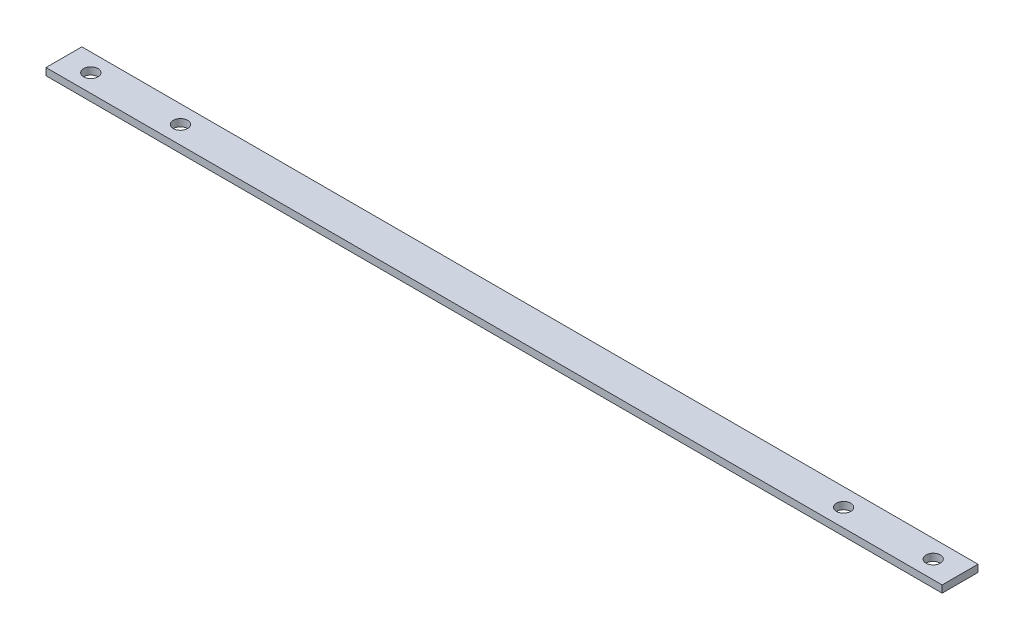
SolidWorks part; units mm, degrees
ref_plane "Спереди" through (0, 0, 0) normal (0, 0, 1) x (1, 0, 0)
ref_plane "Сверху" through (0, 0, 0) normal (0, 1, 0) x (1, 0, 0)
ref_plane "Справа" through (0, 0, 0) normal (1, 0, 0) x (0, 0, -1)
sketch "Эскиз1" plane through (0, 0, 0) normal (1, 0, 0) x (0, 0, -1)
  line L0 (0, 0) -> (20, 0)
extrude "Вытянуть-Тонкостенный1" add sketch "Эскиз1" along normal blind 500 thin thin type one direction wall 4
sketch "Эскиз2" plane through (0, 0, 0) normal (0, 1, 0) x (1, 0, 0)
  circle A0 centre (15, 10) radius 4
  circle A1 centre (65, 10) radius 4
  circle A2 centre (435, 10) radius 4
  circle A3 centre (485, 10) radius 4
  dimension "D1" = 2
  dimension "D2" = 2
extrude "Вырез-Вытянуть1" cut sketch "Эскиз2" against normal through all
